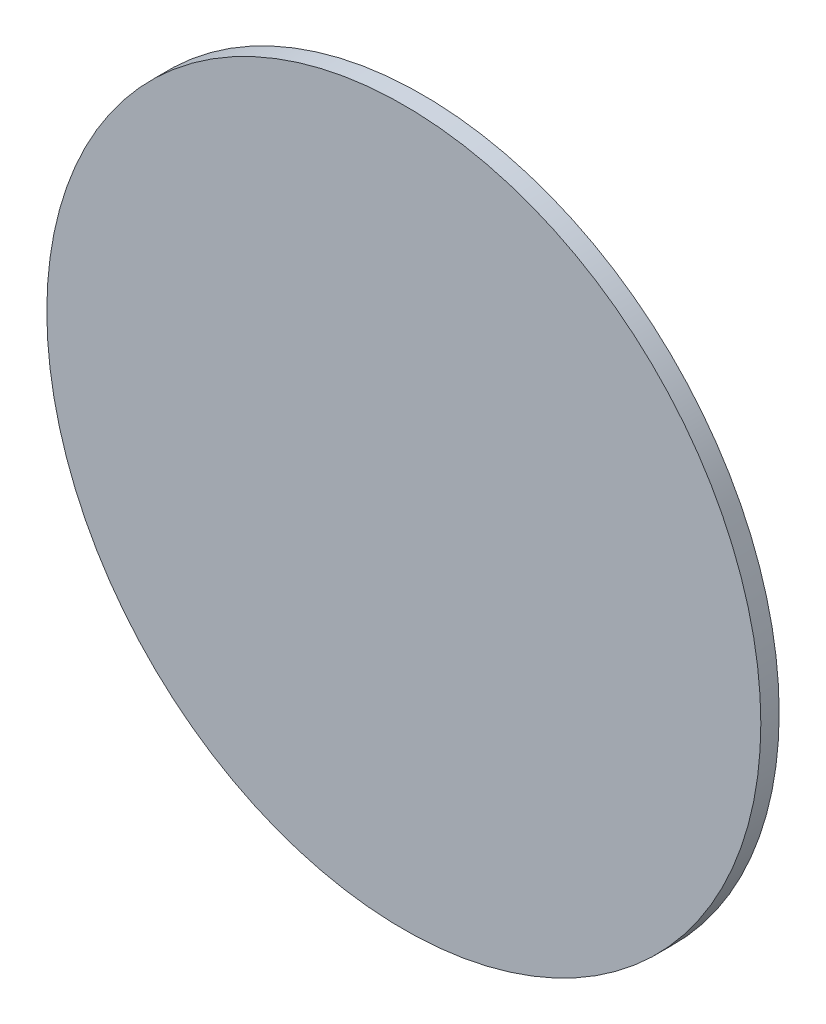
SolidWorks part; units mm, degrees
ref_plane "Front Plane" through (0, 0, 0) normal (0, 0, 1) x (1, 0, 0)
ref_plane "Top Plane" through (0, 0, 0) normal (0, 1, 0) x (1, 0, 0)
ref_plane "Right Plane" through (0, 0, 0) normal (1, 0, 0) x (0, 0, -1)
sketch "Sketch1" plane through (0, 0, 0) normal (0, 0, 1) x (1, 0, 0)
  circle A0 centre (0, 0) radius 19.4584
base flange "Base-Flange1" sketch "Sketch1" thickness 1 reverse thickness direction no parameters "D1"=1
sketch "Bend-Lines1" [suppressed] plane through (0, 0, 0) normal (0, 1, 0) x (1, 0, 0)
sketch "Bounding-Box1" [suppressed] plane through (0, 0, 0) normal (0, 1, 0) x (1, 0, 0)
sheet metal parameters "Sheet-Metal1" thickness 1 parameters "D1"=1
flat pattern "Flat-Pattern1" [suppressed]
sketch "Bend-Lines2" plane through (0, 0, 0) normal (0, 1, 0) x (1, 0, 0)
sketch3d "Bounding-Box2" [suppressed]
  line L0 (-19.4083, 19.5083, 0) -> (-19.5083, -19.4083, 0) construction
  line L1 (19.5083, 19.4083, 0) -> (19.4083, -19.5083, 0) construction
  line L2 (-19.4083, 19.5083, 0) -> (19.5083, 19.4083, 0) construction
  line L3 (-19.5083, -19.4083, 0) -> (19.4083, -19.5083, 0) construction
